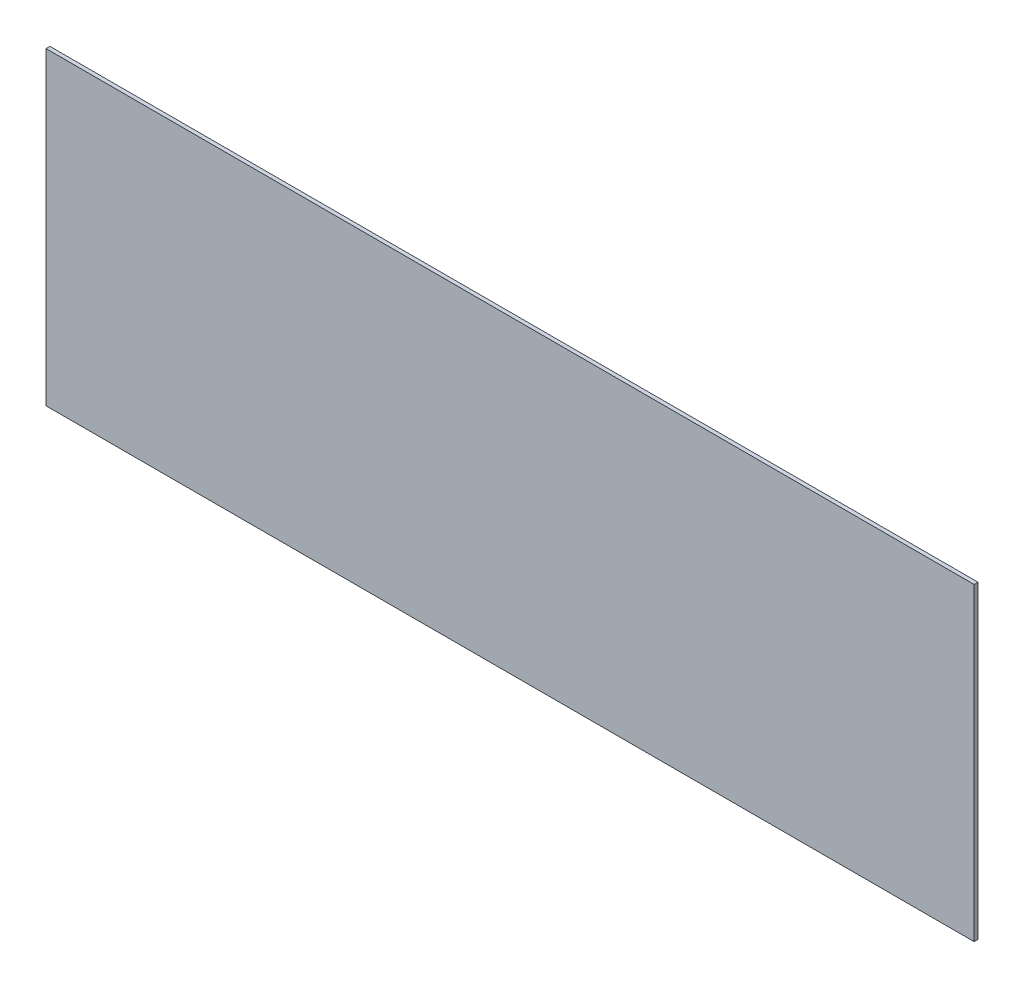
SolidWorks part; units mm, degrees
ref_plane "Front Plane" through (0, 0, 0) normal (0, 0, 1) x (1, 0, 0)
ref_plane "Top Plane" through (0, 0, 0) normal (0, 1, 0) x (1, 0, 0)
ref_plane "Right Plane" through (0, 0, 0) normal (1, 0, 0) x (0, 0, -1)
sketch "Sketch1" plane through (0, 0, 0) normal (0, 0, 1) x (1, 0, 0)
  line L1 (0, 0) -> (609.6, 0)
  line L2 (0, 0) -> (0, 203.2)
  line L3 (0, 203.2) -> (609.6, 203.2)
  line L4 (609.6, 0) -> (609.6, 203.2)
  dimension "D1" = 609.6
  dimension "D2" = 203.2
extrude "Boss-Extrude1" add sketch "Sketch1" along normal blind 2.54
